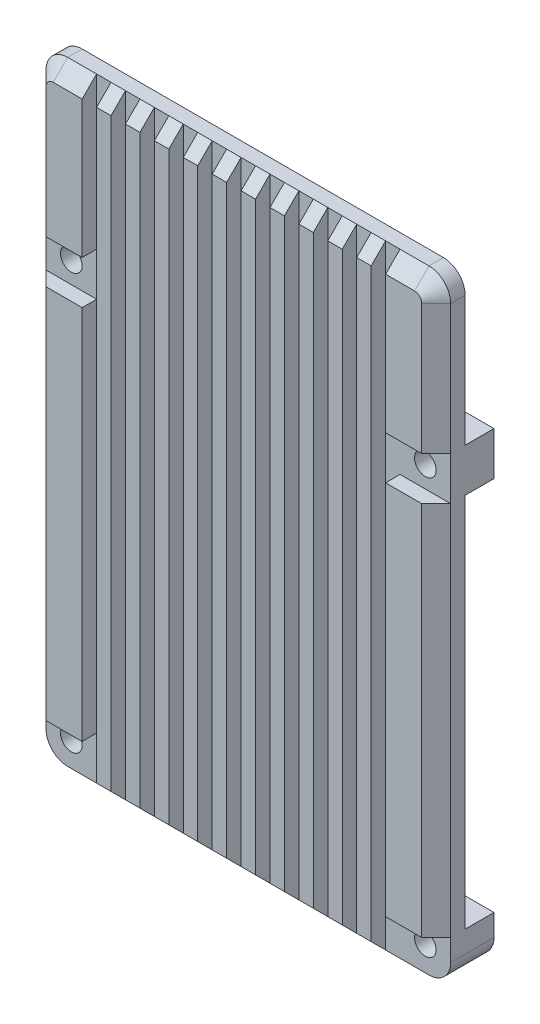
SolidWorks part; units mm, degrees
ref_plane "前视基准面" through (0, 0, 0) normal (0, 0, 1) x (1, 0, 0)
ref_plane "上视基准面" through (0, 0, 0) normal (0, 1, 0) x (1, 0, 0)
ref_plane "右视基准面" through (0, 0, 0) normal (1, 0, 0) x (0, 0, -1)
sketch "草图4" plane through (0, 0, 0) normal (0, 0, 1) x (1, 0, 0)
  line L5 (0, 3) -> (0, 82)
  line L7 (53, 0) -> (3, 0)
  line L8 (56, 82) -> (56, 3)
  line L9 (53, 85) -> (3, 85)
  circle A8 centre (3.5, 3.5) radius 1.5
  circle A9 centre (52.5, 3.5) radius 1.5
  circle A10 centre (52.5, 61) radius 1.5
  circle A11 centre (3.5, 61) radius 1.5
  arc A12 (0, 3) -> (3, 0) centre (3, 3) ccw
  arc A13 (53, 0) -> (56, 3) centre (53, 3) ccw
  arc A14 (56, 82) -> (53, 85) centre (53, 82) ccw
  arc A15 (3, 85) -> (0, 82) centre (3, 82) ccw
  dimension "D3" = 3
  dimension "D4" = 3
  dimension "D1" = 85
  dimension "D2" = 56
  dimension "D5" = 3.5
  dimension "D6" = 3.5
  dimension "D7" = 57.5
  dimension "D8" = 49
extrude "凸台-拉伸1" add sketch "草图4" along normal blind 4
chamfer "倒角1" distance 2 angle 45 8 edges at (56, 42.5, 4) (55.1213, 84.1213, 4) (55.1213, 0.8787, 4) (28, 85, 4) (28, 0, 4) (0.8787, 84.1213, 4) (0.8787, 0.8787, 4) (0, 42.5, 4)
sketch "草图5" plane through (0, 0, 4) normal (0, 0, 1) x (1, 0, 0)
  line L0 (0, 82) -> (0, 3) construction
  line L1 (0, 64) -> (7, 64)
  line L2 (0, 64) -> (0, 58)
  line L3 (0, 58) -> (7, 58)
  line L5 (28, 91.5285) -> (28, -17.4597) construction
  line L6 (56, 58) -> (49, 58)
  line L8 (56, 64) -> (49, 64)
  line L9 (56, 64) -> (56, 58)
  line L10 (56, 0) -> (49, 0)
  line L12 (56, 6) -> (49, 6)
  line L13 (56, 6) -> (56, 0)
  line L14 (0, 6) -> (0, 0)
  line L15 (0, 6) -> (7, 6)
  line L17 (0, 0) -> (7, 0)
  line L18 (53, 85) -> (3, 85) construction
  line L19 (3, 0) -> (53, 0) construction
  line L20 (7, 85) -> (9, 85)
  line L21 (7, 85) -> (7, 64)
  line L22 (7, 0) -> (9, 0)
  line L23 (9, 85) -> (9, 0)
  line L24 (11, 85) -> (11, 0)
  line L25 (11, 85) -> (13, 85)
  line L26 (13, 85) -> (13, 0)
  line L27 (11, 0) -> (13, 0)
  line L28 (15, 85) -> (15, 0)
  line L29 (15, 85) -> (17, 85)
  line L30 (17, 85) -> (17, 0)
  line L31 (15, 0) -> (17, 0)
  line L32 (19, 85) -> (19, 0)
  line L33 (19, 85) -> (21, 85)
  line L34 (21, 85) -> (21, 0)
  line L35 (19, 0) -> (21, 0)
  line L36 (23, 85) -> (23, 0)
  line L37 (23, 85) -> (25, 85)
  line L38 (25, 85) -> (25, 0)
  line L39 (23, 0) -> (25, 0)
  line L40 (27, 85) -> (27, 0)
  line L41 (27, 85) -> (29, 85)
  line L42 (29, 85) -> (29, 0)
  line L43 (27, 0) -> (29, 0)
  line L44 (31, 85) -> (31, 0)
  line L45 (31, 85) -> (33, 85)
  line L46 (33, 85) -> (33, 0)
  line L47 (31, 0) -> (33, 0)
  line L48 (35, 85) -> (35, 0)
  line L49 (35, 85) -> (37, 85)
  line L50 (37, 85) -> (37, 0)
  line L51 (35, 0) -> (37, 0)
  line L52 (39, 85) -> (39, 0)
  line L53 (39, 85) -> (41, 85)
  line L54 (41, 85) -> (41, 0)
  line L55 (39, 0) -> (41, 0)
  line L56 (43, 85) -> (43, 0)
  line L57 (43, 85) -> (45, 85)
  line L58 (45, 85) -> (45, 0)
  line L59 (43, 0) -> (45, 0)
  line L60 (47, 85) -> (47, 0)
  line L61 (47, 85) -> (49, 85)
  line L62 (49, 85) -> (49, 64)
  line L63 (47, 0) -> (49, 0)
  line L64 (7, 58) -> (7, 6)
  line L66 (49, 58) -> (49, 6)
  point P7 (3.5, 61)
  point P25 (28, 85)
  dimension "D1" = 7
  dimension "D2" = 6
  dimension "D4" = 2
  dimension "D3" = 2
  dimension "D5" = 11
extrude "切除-拉伸1" cut sketch "草图5" against normal blind 2 contours L46 L44 | L3 L64 L15 L23 L21 L1 | L34 L32 | L24 L27 L26 L25 | L28 L31 L30 L29 | L36 L39 L38 L37 | L40 L43 L42 L41 | L48 L51 L50 L49 | L54 L55 L52 L53 | L56 L59 L58 L57 | L60 L63 L10 L13 L12 L66 L6 L9 L8 L62 L61 region at (3.5, 63.1452, 4) region at (20, 42.5, 4) region at (32, 42.5, 4)
sketch "草图6" plane through (0, 0, 0) normal (0, 0, -1) x (-1, 0, 0)
  line L1 (-56, 64) -> (-49, 64)
  line L2 (-56, 64) -> (-56, 58)
  line L3 (-56, 58) -> (-49, 58)
  line L4 (-49, 64) -> (-49, 58)
  line L5 (-56, 6) -> (-49, 6)
  line L6 (-56, 6) -> (-56, 3)
  line L7 (-53, 0) -> (-49, 0)
  line L8 (-49, 6) -> (-49, 0)
  line L9 (-7, 6) -> (0, 6)
  line L10 (-7, 6) -> (-7, 0)
  line L11 (-7, 0) -> (-3, 0)
  line L12 (0, 6) -> (0, 3)
  line L13 (-7, 64) -> (0, 64)
  line L14 (-7, 64) -> (-7, 58)
  line L15 (-7, 58) -> (0, 58)
  line L16 (0, 64) -> (0, 58)
  arc A0 (-3, 0) -> (0, 3) centre (-3, 3) ccw construction
  arc A1 (-56, 3) -> (-53, 0) centre (-53, 3) ccw construction
  arc A2 (-3, 0) -> (0, 3) centre (-3, 3) ccw
  arc A3 (-56, 3) -> (-53, 0) centre (-53, 3) ccw
  circle A4 centre (-52.5, 3.5) radius 1.5 construction
  circle A5 centre (-3.5, 3.5) radius 1.5 construction
  circle A6 centre (-3.5, 61) radius 1.5 construction
  circle A7 centre (-52.5, 61) radius 1.5 construction
  circle A8 centre (-52.5, 3.5) radius 1.5
  circle A9 centre (-3.5, 3.5) radius 1.5
  circle A10 centre (-3.5, 61) radius 1.5
  circle A11 centre (-52.5, 61) radius 1.5
extrude "凸台-拉伸2" add sketch "草图6" along normal blind 4
